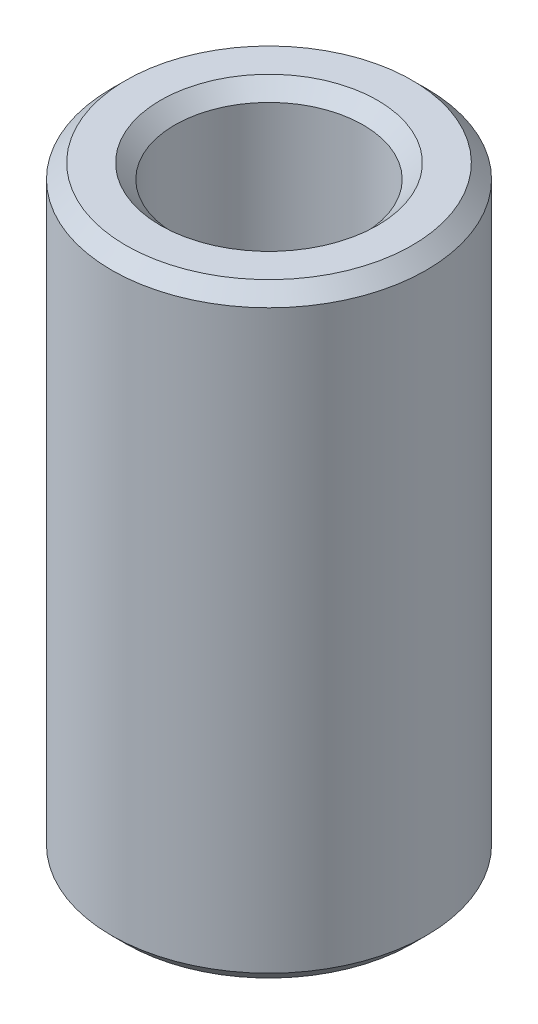
SolidWorks part; units mm, degrees
ref_plane "Front Plane" through (0, 0, 0) normal (0, 0, 1) x (1, 0, 0)
ref_plane "Top Plane" through (0, 0, 0) normal (0, 1, 0) x (1, 0, 0)
ref_plane "Right Plane" through (0, 0, 0) normal (1, 0, 0) x (0, 0, -1)
sketch "Sketch1" plane through (0, 0, 0) normal (0, 1, 0) x (1, 0, 0)
  circle A0 centre (0, 0) radius 15
  dimension "SLEEVE_OD" = 30
extrude "Boss-Extrude1" add sketch "Sketch1" along normal blind 57.6517
sketch "Sketch2" plane through (0, 0, 0) normal (0, 1, 0) x (1, 0, 0)
  circle A0 centre (0, 0) radius 8.9801
  dimension "BORE_D" = 17.9603
extrude "Cut-Extrude1" cut sketch "Sketch2" along normal through all
chamfer "Chamfer1" distance 1.3609 angle 45 4 edges at (0, 57.6517, 8.9801) (0, 0, 8.9801) (0, 0, 15) (0, 57.6517, 15)
